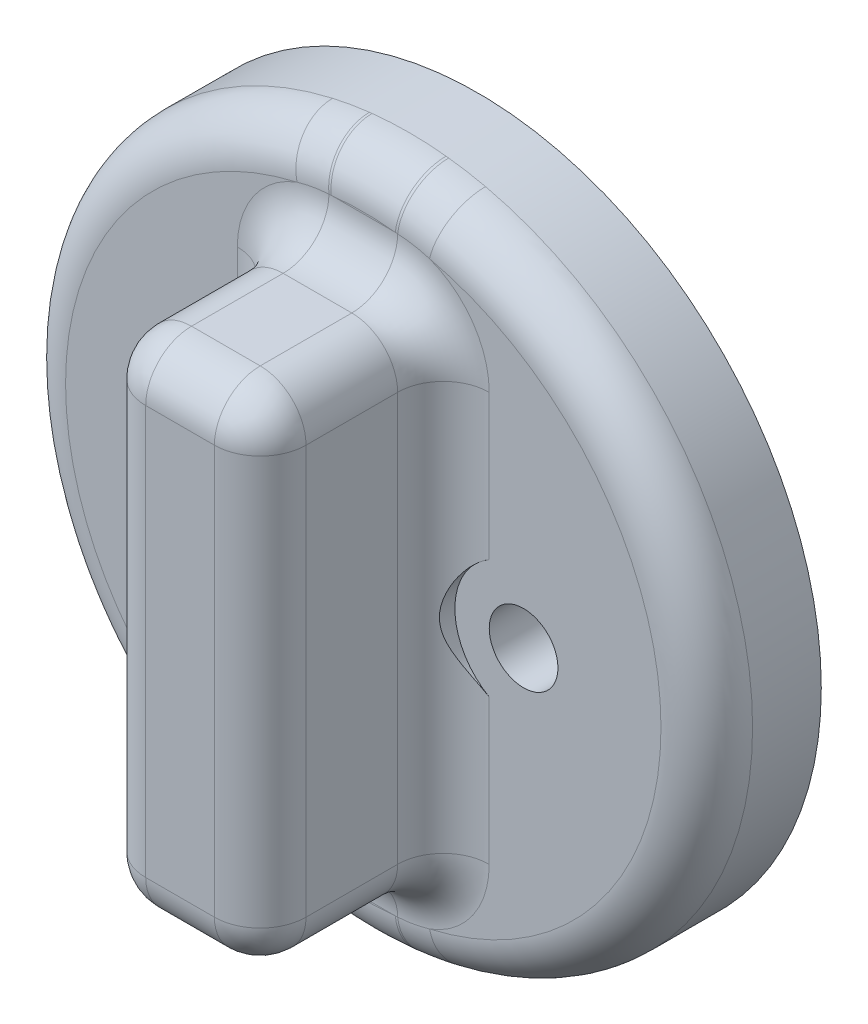
SolidWorks part; units mm, degrees
material "6061 Alloy"
ref_plane "Front Plane" through (0, 0, 0) normal (0, 0, 1) x (1, 0, 0)
ref_plane "Top Plane" through (0, 0, 0) normal (0, 1, 0) x (1, 0, 0)
ref_plane "Right Plane" through (0, 0, 0) normal (1, 0, 0) x (0, 0, -1)
sketch "Sketch2" plane through (0, 0, 0) normal (0, 0, 1) x (1, 0, 0)
  circle A0 centre (0, 0) radius 15
  dimension "D1" = 30
extrude "Boss-Extrude2" add sketch "Sketch2" along normal blind 5
sketch "Sketch3" plane through (0, 0, 5) normal (0, 0, 1) x (1, 0, 0)
  line L1 (-3.5, 10.9245) -> (3.5, 10.9245)
  line L2 (-3.5, 10.9245) -> (-3.5, -10.9245)
  line L3 (-3.5, -10.9245) -> (3.5, -10.9245)
  line L4 (3.5, 10.9245) -> (3.5, -10.9245)
  line L5 (0, -10.9245) -> (0, 10.9245) construction
  line L6 (-3.5, 0) -> (3.5, 0) construction
  point P0 (0, 0)
  dimension "D1" = 7
extrude "Boss-Extrude4" add sketch "Sketch3" along normal blind 8
fillet "Fillet1" radius 2 12 edges at (3.5, 0, 5) (3.5, 10.9245, 9) (0, 10.9245, 5) (-3.5, 10.9245, 9) (-3.5, 0, 5) (-3.5, -10.9245, 9) (3.5, -10.9245, 9) (0, -10.9245, 5) (0, -10.9245, 13) (-3.5, 0, 13) (0, 10.9245, 13) (3.5, 0, 13)
fillet "Fillet2" radius 2 1 edges at (15, 0, 5)
sketch "Sketch4" plane through (0, 0, 0) normal (0, 0, 1) x (1, 0, 0)
  line L0 (-7, 0) -> (0, 0) construction
  line L1 (0, 0) -> (0, -4.7782) construction
  circle A0 centre (-7, 0) radius 1.5
  circle A1 centre (7, 0) radius 1.5
  dimension "D1" = 3
  dimension "D2" = 7
extrude "M4_DRILL" cut sketch "Sketch4" along normal up to surface (5 mm away) up to face at (7.0172, 0, 5)
sketch "Sketch5" plane through (0, 0, 5) normal (0, 0, 1) x (1, 0, 0)
  circle A0 centre (-7, 0) radius 3
  circle A1 centre (7, 0) radius 3
  dimension "D1" = 6
  dimension "D2" = 6
extrude "Cut-Extrude1" cut sketch "Sketch5" along normal up to surface (8 mm away) up to face at (0, 0, 13)
